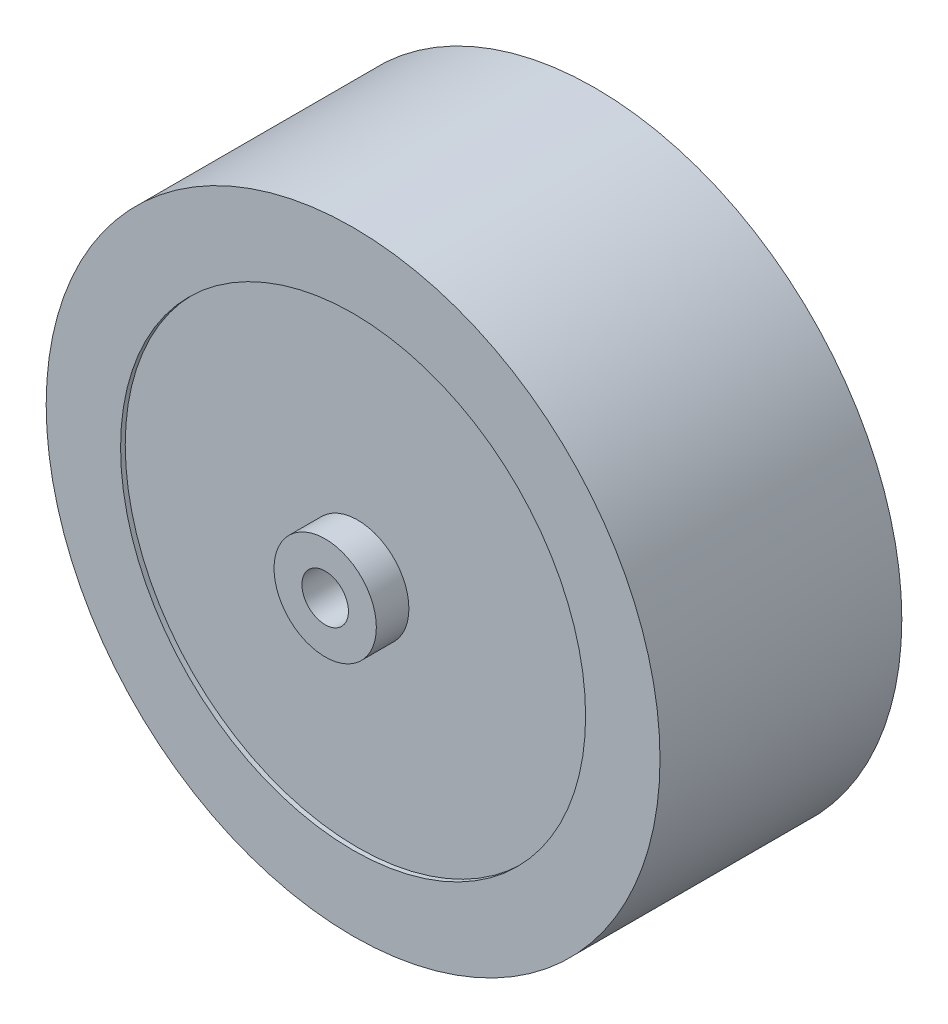
SolidWorks part; units mm, degrees
ref_plane "Piano frontale" through (0, 0, 0) normal (0, 0, 1) x (1, 0, 0)
ref_plane "Piano superiore" through (0, 0, 0) normal (0, 1, 0) x (1, 0, 0)
ref_plane "Piano destro" through (0, 0, 0) normal (1, 0, 0) x (0, 0, -1)
sketch "Schizzo1" plane through (0, 0, 0) normal (0, 0, 1) x (1, 0, 0)
  circle A0 centre (0, 0) radius 25
  circle A1 centre (0, 0) radius 33
  circle A2 centre (0, 0) radius 2.5
  dimension "D1" = 66
  dimension "D2" = 50
  dimension "D3" = 5
extrude "Estrusione-Estrusione1" add sketch "Schizzo1" along normal blind 13 and the other way blind 13 contours A1 A0 region at (-32.0666, 0, 0)
extrude "Estrusione-Estrusione2" add sketch "Schizzo1<3>" along normal blind 12.5 and the other way blind 12.5 contours A0 A2 region at (-24.2929, 0, 0)
sketch "Schizzo1<3>" plane through (0, 0, 0) normal (0, 0, 1) x (1, 0, 0) same geometry as "Schizzo1"
sketch "Schizzo2" plane through (0, 0, 12.5) normal (0, 0, 1) x (1, 0, 0)
  circle A0 centre (0, 0) radius 5.5
  circle M1 centre (0, 0) radius 2.5
  dimension "D1" = 11
extrude "Estrusione-Estrusione3" add sketch "Schizzo2" along normal blind 3.5 contours A0 M1 region at (-5.3444, 0, 12.5)
